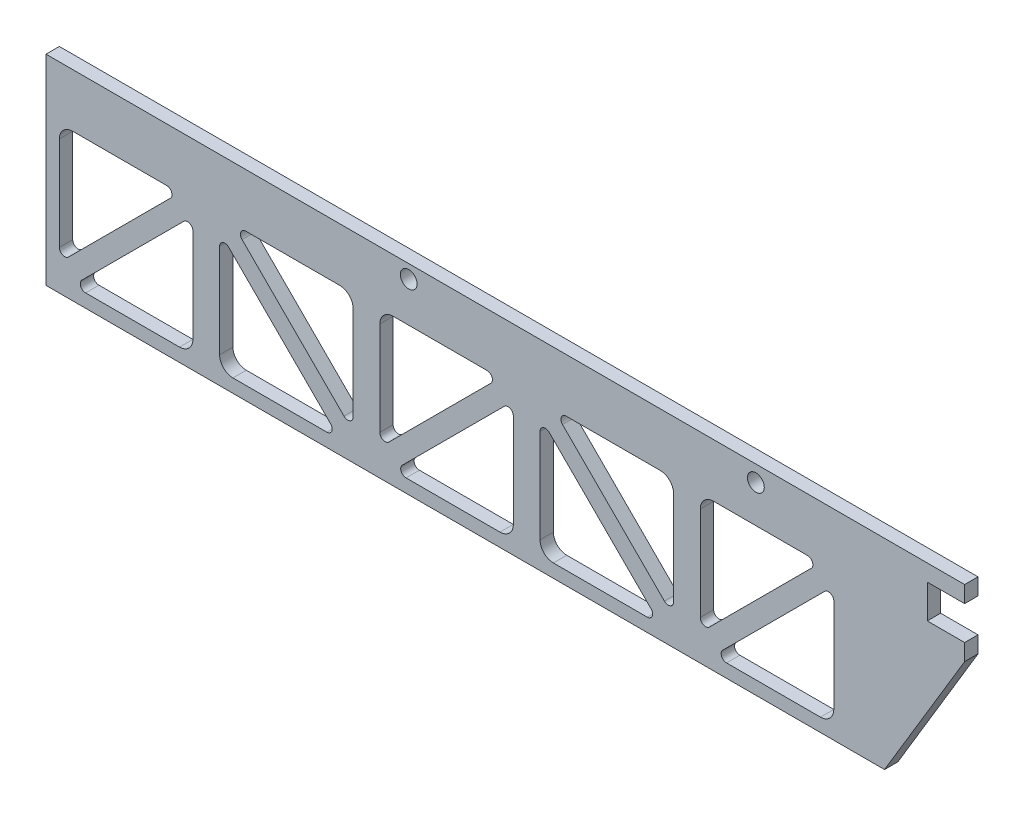
SolidWorks part; units mm, degrees
material "Pine"
ref_plane "Front Plane" through (0, 0, 0) normal (0, 0, 1) x (1, 0, 0)
ref_plane "Top Plane" through (0, 0, 0) normal (0, 1, 0) x (1, 0, 0)
ref_plane "Right Plane" through (0, 0, 0) normal (1, 0, 0) x (0, 0, -1)
sketch "Model" plane through (0, 0, 0) normal (0, 0, 1) x (1, 0, 0)
  line L8 (171.2321, 6.35) -> (215.9, 6.35)
  line L9 (217.9139, 59.1639) -> (169.4361, 10.6861)
  line L10 (222.25, 57.3679) -> (222.25, 12.7)
  line L11 (234.95, 57.3679) -> (234.95, 12.7)
  line L12 (239.2861, 59.1639) -> (287.7639, 10.6861)
  line L13 (241.3, 6.35) -> (285.9679, 6.35)
  line L14 (294.1139, 17.0361) -> (245.6361, 65.5139)
  line L15 (247.4321, 69.85) -> (292.1, 69.85)
  line L16 (298.45, 63.5) -> (298.45, 18.8321)
  line L17 (323.6321, 6.35) -> (368.3, 6.35)
  line L18 (370.3139, 59.1639) -> (321.8361, 10.6861)
  line L19 (374.65, 57.3679) -> (374.65, 12.7)
  line L20 (18.8321, 6.35) -> (63.5, 6.35)
  line L21 (17.0361, 10.6861) -> (65.5139, 59.1639)
  line L22 (69.85, 57.3679) -> (69.85, 12.7)
  line L23 (82.55, 57.3679) -> (82.55, 12.7)
  line L24 (86.8861, 59.1639) -> (135.3639, 10.6861)
  line L25 (88.9, 6.35) -> (133.5679, 6.35)
  line L26 (93.2361, 65.5139) -> (141.7139, 17.0361)
  line L27 (95.0321, 69.85) -> (139.7, 69.85)
  line L28 (146.05, 63.5) -> (146.05, 18.8321)
  line L29 (163.0861, 17.0361) -> (211.5639, 65.5139)
  line L30 (158.75, 63.5) -> (158.75, 18.8321)
  line L31 (165.1, 69.85) -> (209.7679, 69.85)
  line L32 (315.4861, 17.0361) -> (363.9639, 65.5139)
  line L33 (311.15, 63.5) -> (311.15, 18.8321)
  line L34 (317.5, 69.85) -> (362.1679, 69.85)
  line L35 (419.1, 87.376) -> (419.1, 71.374)
  line L36 (436.88, 87.376) -> (419.1, 87.376)
  line L37 (436.88, 87.376) -> (436.88, 95.25)
  line L38 (0, 95.25) -> (436.88, 95.25)
  line L39 (0, 0) -> (0, 95.25)
  line L40 (0, 0) -> (398.78, 0)
  line L41 (436.88, 63.5) -> (398.78, 0)
  line L42 (436.88, 63.5) -> (436.88, 71.374)
  line L43 (419.1, 71.374) -> (436.88, 71.374)
  line L44 (6.35, 63.5) -> (6.35, 18.8321)
  line L45 (12.7, 69.85) -> (57.3679, 69.85)
  line L46 (59.1639, 65.5139) -> (10.6861, 17.0361)
  arc A0 (215.9, 6.35) -> (222.25, 12.7) centre (215.9, 12.7) ccw
  arc A1 (169.4361, 10.6861) -> (171.2321, 6.35) centre (171.2321, 8.89) ccw
  arc A2 (222.25, 57.3679) -> (217.9139, 59.1639) centre (219.71, 57.3679) ccw
  arc A3 (239.2861, 59.1639) -> (234.95, 57.3679) centre (237.49, 57.3679) ccw
  arc A4 (285.9679, 6.35) -> (287.7639, 10.6861) centre (285.9679, 8.89) ccw
  arc A5 (234.95, 12.7) -> (241.3, 6.35) centre (241.3, 12.7) ccw
  arc A6 (247.4321, 69.85) -> (245.6361, 65.5139) centre (247.4321, 67.31) ccw
  arc A7 (298.45, 63.5) -> (292.1, 69.85) centre (292.1, 63.5) ccw
  arc A8 (294.1139, 17.0361) -> (298.45, 18.8321) centre (295.91, 18.8321) ccw
  arc A9 (321.8361, 10.6861) -> (323.6321, 6.35) centre (323.6321, 8.89) ccw
  arc A10 (374.65, 57.3679) -> (370.3139, 59.1639) centre (372.11, 57.3679) ccw
  arc A11 (368.3, 6.35) -> (374.65, 12.7) centre (368.3, 12.7) ccw
  arc A12 (63.5, 6.35) -> (69.85, 12.7) centre (63.5, 12.7) ccw
  arc A13 (17.0361, 10.6861) -> (18.8321, 6.35) centre (18.8321, 8.89) ccw
  arc A14 (69.85, 57.3679) -> (65.5139, 59.1639) centre (67.31, 57.3679) ccw
  arc A15 (86.8861, 59.1639) -> (82.55, 57.3679) centre (85.09, 57.3679) ccw
  arc A16 (133.5679, 6.35) -> (135.3639, 10.6861) centre (133.5679, 8.89) ccw
  arc A17 (82.55, 12.7) -> (88.9, 6.35) centre (88.9, 12.7) ccw
  arc A18 (95.0321, 69.85) -> (93.2361, 65.5139) centre (95.0321, 67.31) ccw
  arc A19 (146.05, 63.5) -> (139.7, 69.85) centre (139.7, 63.5) ccw
  arc A20 (141.7139, 17.0361) -> (146.05, 18.8321) centre (143.51, 18.8321) ccw
  arc A21 (158.75, 18.8321) -> (163.0861, 17.0361) centre (161.29, 18.8321) ccw
  arc A22 (165.1, 69.85) -> (158.75, 63.5) centre (165.1, 63.5) ccw
  arc A23 (211.5639, 65.5139) -> (209.7679, 69.85) centre (209.7679, 67.31) ccw
  arc A24 (363.9639, 65.5139) -> (362.1679, 69.85) centre (362.1679, 67.31) ccw
  arc A25 (311.15, 18.8321) -> (315.4861, 17.0361) centre (313.69, 18.8321) ccw
  arc A26 (317.5, 69.85) -> (311.15, 63.5) centre (317.5, 63.5) ccw
  arc A27 (6.35, 18.8321) -> (10.6861, 17.0361) centre (8.89, 18.8321) ccw
  arc A28 (12.7, 69.85) -> (6.35, 63.5) centre (12.7, 63.5) ccw
  arc A29 (59.1639, 65.5139) -> (57.3679, 69.85) centre (57.3679, 67.31) ccw
  circle A30 centre (172.4917, 88.8013) radius 4
  circle A31 centre (337.5917, 87.63) radius 4
  dimension "D2" = 6.4487
  dimension "D3" = 172.4917
  dimension "D4" = 8
  dimension "D5" = 7.62
  dimension "D6" = 8
  dimension "D1" = 95.25
  dimension "D7" = 165.1
extrude "Boss-Extrude2" add sketch "Model" along normal blind 6.35
